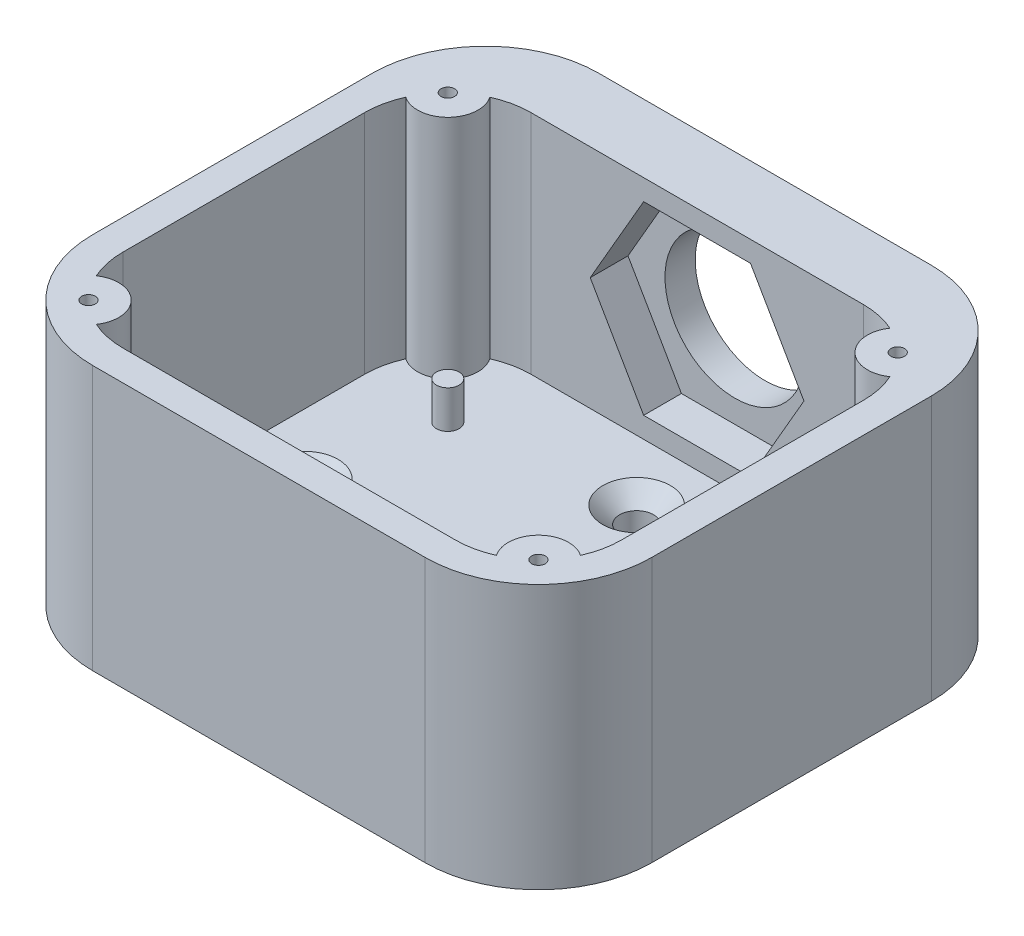
SolidWorks part; units mm, degrees
ref_plane "Alzado" through (0, 0, 0) normal (0, 0, 1) x (1, 0, 0)
ref_plane "Planta" through (0, 0, 0) normal (0, 1, 0) x (1, 0, 0)
ref_plane "Vista lateral" through (0, 0, 0) normal (1, 0, 0) x (0, 0, -1)
sketch "Croquis1" plane through (0, 0, 0) normal (0, 1, 0) x (1, 0, 0)
  line L0 (3, 0) -> (47, 0)
  line L1 (50, 3) -> (50, 35)
  line L2 (47, 38) -> (3, 38)
  line L3 (0, 35) -> (0, 3)
  arc A0 (47, 0) -> (50, 3) centre (47, 3) ccw
  arc A1 (50, 35) -> (47, 38) centre (47, 35) ccw
  arc A2 (3, 38) -> (0, 35) centre (3, 35) ccw
  arc A3 (0, 3) -> (3, 0) centre (3, 3) ccw
  circle A4 centre (47, 35) radius 1.5
  circle A5 centre (3, 3) radius 1.5
  circle A6 centre (47, 3) radius 1.5
sketch "Croquis2" plane through (0, 0, 0) normal (0, 1, 0) x (1, 0, 0)
  line L4 (62, 3) -> (62, 35)
  line L6 (-12, 35) -> (-12, 3)
  line L7 (3, -12) -> (47, -12)
  line L8 (58, 3) -> (58, 35)
  line L9 (3, -8) -> (47, -8)
  line L10 (-8, 35) -> (-8, 3)
  line L11 (47, 46) -> (3, 46)
  line L12 (58, 3) -> (58, 35)
  line L13 (3, -8) -> (47, -8)
  line L14 (-8, 35) -> (-8, 3)
  line L15 (47, 46) -> (3, 46)
  line L16 (-12, 35) -> (-12, 40)
  line L17 (47, 50) -> (3, 50) construction
  line L20 (3, 55) -> (47, 55)
  line L21 (62, 40) -> (62, 35)
  arc A6 (-12, 3) -> (3, -12) centre (3, 3) ccw
  arc A7 (47, -12) -> (62, 3) centre (47, 3) ccw
  arc A8 (58, 35) -> (47, 46) centre (47, 35) ccw
  arc A9 (47, -8) -> (58, 3) centre (47, 3) ccw
  arc A10 (-8, 3) -> (3, -8) centre (3, 3) ccw
  arc A11 (3, 46) -> (-8, 35) centre (3, 35) ccw
  arc A12 (58, 35) -> (47, 46) centre (47, 35) ccw
  arc A13 (47, -8) -> (58, 3) centre (47, 3) ccw
  arc A14 (-8, 3) -> (3, -8) centre (3, 3) ccw
  arc A15 (3, 46) -> (-8, 35) centre (3, 35) ccw
  arc A16 (47, 55) -> (62, 40) centre (47, 40) cw
  arc A17 (-12, 40) -> (3, 55) centre (3, 40) cw
  arc A18 (3, 50) -> (-12, 35) centre (3, 35) ccw construction
  arc A20 (62, 35) -> (47, 50) centre (47, 35) ccw construction
  point P20 (-12, 55)
  dimension "D4" = 15
  dimension "D3" = 20
  dimension "D1" = 8
  dimension "D2" = 4
extrude "Saliente-Extruir1" add sketch "Croquis2" along normal blind 35
extrude "Saliente-Extruir2" add sketch "Croquis2<2>" along normal blind 5 contours L15 A15 L14 A14 L13 A13 L12 A12 region at (25, 0, -19)
sketch "Croquis2<2>" plane through (0, 0, 0) normal (0, 1, 0) x (1, 0, 0) same geometry as "Croquis2"
sketch "Croquis3" plane through (0, 0, -46) normal (0, 0, 1) x (1, 0, 0)
  line L0 (3, 35) -> (47, 5) construction
  line L1 (39.1451, 20) -> (32.0725, 32.25)
  line L2 (32.0725, 32.25) -> (17.9275, 32.25)
  line L3 (17.9275, 32.25) -> (10.8549, 20)
  line L4 (10.8549, 20) -> (17.9275, 7.75)
  line L5 (17.9275, 7.75) -> (32.0725, 7.75)
  line L6 (32.0725, 7.75) -> (39.1451, 20)
  line L7 (47, 5) -> (3, 5) construction
  circle A0 centre (25, 20) radius 12.25 construction
  point P12 (0, 0)
  point P13 (25, 20)
  point P16 (0, 0)
  dimension "D1" = 24.5
extrude "Cortar-Extruir1" cut sketch "Croquis3" against normal blind 5
sketch "Croquis4" plane through (0, 0, -51) normal (0, 0, 1) x (1, 0, 0)
  circle A0 centre (25, 20) radius 9.25
  point P2 (0, 0)
  point P3 (25.4479, 13.1464)
  dimension "D1" = 18.5
extrude "Cortar-Extruir2" cut sketch "Croquis4" against normal blind 5
hole_wizard "Refrentado para tornillo tapón con cabeza plana de clavija de M41" positions "Croquis5" profile "Croquis6" countersink size "M4" standard "Ansi Metric" end condition up to next
sketch "Croquis5" plane through (0, 5, 0) normal (0, 1, 0) x (1, 0, 0)
  line L0 (0, 35) -> (0, 3) construction
  line L1 (50, 3) -> (50, 35) construction
  line L2 (3, 0) -> (47, 0) construction
  line L3 (47, 38) -> (3, 38) construction
  point P0 (0, 19)
  point P4 (50, 19)
  point P8 (25, 0)
  point P12 (25, 38)
sketch "Croquis6" plane through (0, 5, -19) normal (1, 0, 0) x (0, 0, 1)
  line L0 (0, 0) -> (0, 5)
  line L1 (0, 5) -> (2.25, 5)
  line L2 (2.25, 5) -> (2.25, 2.23)
  line L3 (2.25, 2.23) -> (4.48, 0)
  line L5 (4.48, 0) -> (0, 0)
  line L6 (-2.25, 2.23) -> (-4.48, 0) construction
  line L11 (0, -6.35) -> (0, 107.95) construction
  dimension "Diámetro de taladro hasta el siguiente" = 4.5
  dimension "Profundidad de taladro hasta el siguiente" = 5
  dimension "Diámetro de avellanado cercano" = 8.96
  dimension "Ángulo de avellanado cercano" = 90
sketch "Croquis7" plane through (0, 5, 0) normal (0, 1, 0) x (1, 0, 0)
  circle A0 centre (3, 3) radius 0.9
  circle A1 centre (3, 3) radius 2
  circle A2 centre (47, 3) radius 0.9
  circle A3 centre (47, 3) radius 2
  circle A4 centre (47, 35) radius 0.9
  circle A5 centre (47, 35) radius 2
  point P7 (47, 3)
  point P12 (47, 35)
  dimension "D1" = 1.8
  dimension "3." = 4
extrude "Saliente-Extruir3" add sketch "Croquis7" along normal blind 5
sketch "Croquis8" plane through (0, 10, 0) normal (0, 1, 0) x (1, 0, 0)
  circle A0 centre (47, 35) radius 1.5 construction
  circle A1 centre (47, 35) radius 0.9 construction
  circle A2 centre (47, 3) radius 1.5 construction
  circle A3 centre (47, 3) radius 0.9 construction
  circle A4 centre (3, 3) radius 0.9 construction
  circle A5 centre (3, 3) radius 1.5 construction
  circle A6 centre (47, 35) radius 1.5
  circle A7 centre (47, 35) radius 0.9
  circle A8 centre (47, 3) radius 1.5
  circle A9 centre (47, 3) radius 0.9
  circle A10 centre (3, 3) radius 0.9
  circle A11 centre (3, 3) radius 1.5
extrude "Saliente-Extruir4" add sketch "Croquis8" along normal blind 1
sketch "Croquis9" plane through (0, 5, 0) normal (0, 1, 0) x (1, 0, 0)
  circle A0 centre (3, 35) radius 1.5
  dimension "D1" = 3
extrude "Saliente-Extruir5" add sketch "Croquis9" along normal blind 5
sketch "Croquis10" plane through (0, 35, 0) normal (0, 1, 0) x (1, 0, 0)
  circle A2 centre (-4.7782, -4.7782) radius 0.9
  arc A3 (-8, 3) -> (3, -8) centre (3, 3) ccw construction
  circle A4 centre (54.7782, -4.7782) radius 0.9
  arc A5 (47, -8) -> (58, 3) centre (47, 3) ccw construction
  circle A6 centre (-4.7782, 42.7782) radius 0.9
  arc A7 (3, 46) -> (-8, 35) centre (3, 35) ccw construction
  circle A8 centre (54.7782, 42.7782) radius 0.9
  arc A9 (58, 35) -> (47, 46) centre (47, 35) ccw construction
  circle A10 centre (-4.7782, -4.7782) radius 4
  circle A11 centre (-4.7782, 42.7782) radius 4
  circle A12 centre (54.7782, 42.7782) radius 4
  circle A13 centre (54.7782, -4.7782) radius 4
  arc A14 (-12, 3) -> (3, -12) centre (3, 3) ccw construction
  point P24 (-4.7782, -4.7782)
  dimension "D1" = 1.8
extrude "Saliente-Extruir6" add sketch "Croquis10" against normal up to next
extrude "Cortar-Extruir3" cut sketch "Croquis10<2>" against normal up to next contours A6 | A8 | A4 | A2
sketch "Croquis10<2>" plane through (0, 35, 0) normal (0, 1, 0) x (1, 0, 0) same geometry as "Croquis10"
